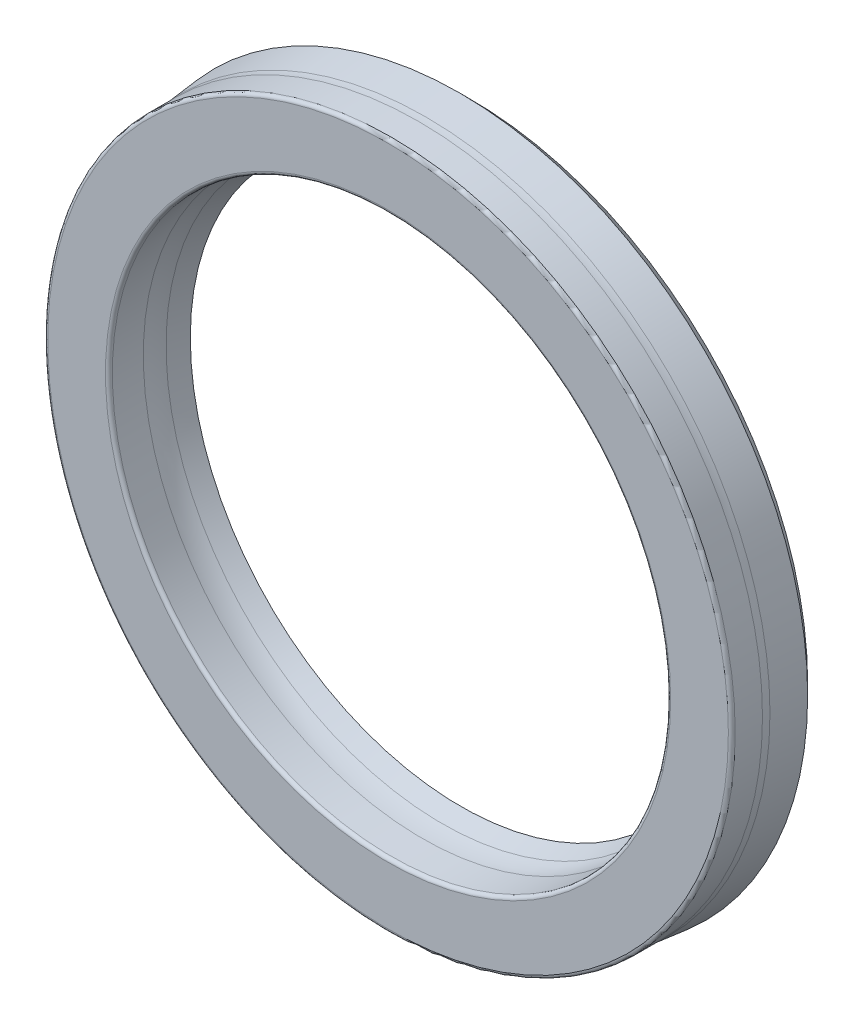
SolidWorks part; units mm, degrees
ref_plane "Front Plane" through (0, 0, 0) normal (0, 0, 1) x (1, 0, 0)
ref_plane "Top Plane" through (0, 0, 0) normal (0, 1, 0) x (1, 0, 0)
ref_plane "Right Plane" through (0, 0, 0) normal (1, 0, 0) x (0, 0, -1)
sketch "Sketch1" plane through (0, 0, 0) normal (1, 0, 0) x (0, 0, -1)
  line L0 (0, 41.25) -> (0, 49.675)
  line L1 (0.5, 50.175) -> (4.4787, 50.175)
  line L2 (5.5185, 50.2292) -> (10.5, 50.75)
  line L3 (10.5, 50.75) -> (12, 49.25)
  line L4 (12, 49.25) -> (12, 47.5)
  line L5 (12, 47.5) -> (7.7114, 46.2075)
  line L7 (5.0212, 40.75) -> (0.5, 40.75)
  line L8 (0, 0) -> (11.0087, 0) construction
  line L9 (7.7348, 44.2858) -> (11.5, 43.25)
  line L10 (11.5, 43.25) -> (11.5, 41)
  line L11 (11.5, 41) -> (10.634, 39.5)
  line L12 (10.634, 39.5) -> (7.9155, 40.322)
  arc A0 (7.7348, 44.2858) -> (7.7114, 46.2075) centre (8, 45.25) cw
  arc A1 (7.9155, 40.322) -> (5.0212, 40.75) centre (5.0212, 30.75) ccw
  arc A2 (0, 49.675) -> (0.5, 50.175) centre (0.5, 49.675) cw
  arc A3 (0.5, 40.75) -> (0, 41.25) centre (0.5, 41.25) cw
  arc A4 (4.4787, 50.175) -> (5.5185, 50.2292) centre (4.4787, 60.175) ccw
  point P15 (6.5, 40.75)
  point P25 (5, 50.175)
  dimension "D8" = 5
  dimension "D9" = 1
  dimension "D19" = 0.5
  dimension "D16" = 90.5
  dimension "D18" = 10
  dimension "D20" = 10
  dimension "D1" = 101.5
  dimension "D2" = 100.35
  dimension "D3" = 81.5
  dimension "D4" = 79
  dimension "D5" = 86.5
  dimension "D6" = 95
  dimension "D7" = 12
  dimension "D10" = 5
  dimension "D11" = 6.5
  dimension "D12" = 1.5
  dimension "D13" = 82
  dimension "D14" = 45
  dimension "D15" = 30
  dimension "D17" = 0.5
revolve "Revolve1" add sketch "Sketch1" angle 360 about L8
ref_axis "Axis1" through (0, 0, -12.6) along (0, 0, 1)
